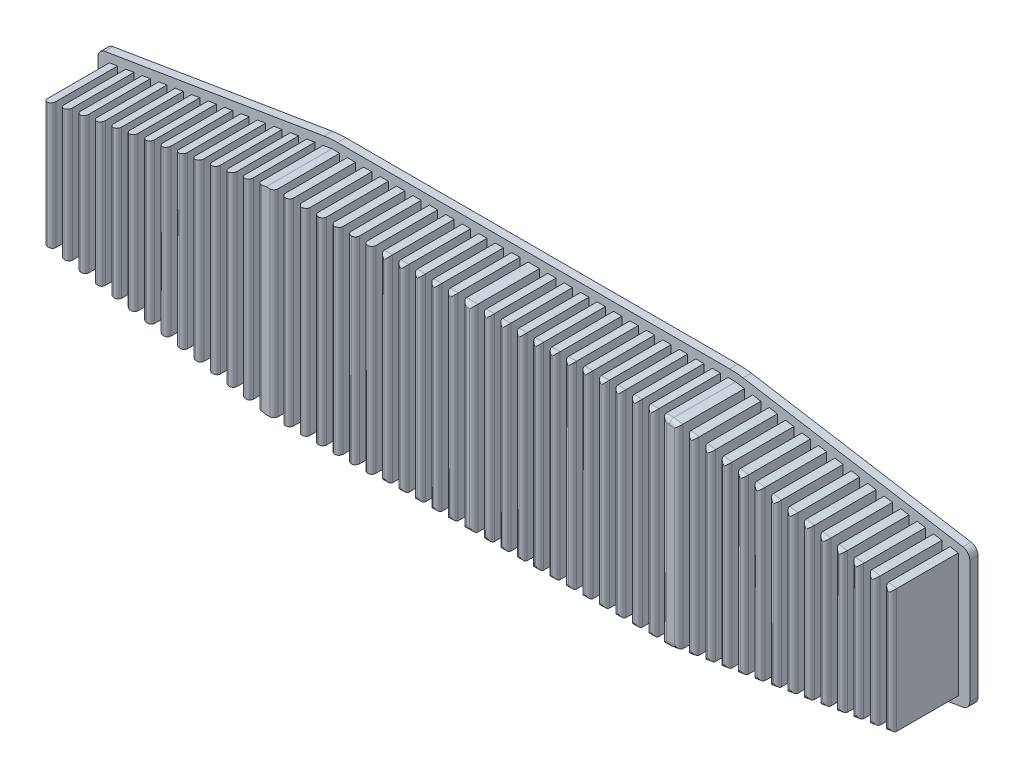
SolidWorks part; units mm, degrees
material "moto_Chrome Stainless Steel"
ref_plane "Front Plane" through (0, 0, 0) normal (0, 0, 1) x (1, 0, 0)
ref_plane "Top Plane" through (0, 0, 0) normal (0, 1, 0) x (1, 0, 0)
ref_plane "Right Plane" through (0, 0, 0) normal (1, 0, 0) x (0, 0, -1)
sketch "Sketch1" plane through (0, 0, 0) normal (0, 0, 1) x (1, 0, 0)
  line L12 (-24.854, 15) -> (-55, 10)
  line L14 (55, 10) -> (24.7913, 15)
  line L16 (-24.854, 15) -> (24.7913, 15)
  line L25 (0, 0) -> (4.6771, 0)
  line L26 (55, -10) -> (24.7913, -15)
  line L27 (-24.854, -15) -> (24.7913, -15)
  line L28 (-24.854, -15) -> (-55, -10)
  line L29 (-24.6892, 13) -> (-53, 8.3044)
  line L30 (-53, 8.3044) -> (-53, -8.3044)
  line L31 (-24.6892, -13) -> (-53, -8.3044)
  line L32 (-24.6892, -13) -> (24.6269, -13)
  line L33 (53, -8.3038) -> (24.6269, -13)
  line L34 (53, 8.3038) -> (53, -8.3038)
  line L35 (53, 8.3038) -> (24.6269, 13)
  line L36 (-55, 10) -> (-55, -10)
  line L37 (55, 10) -> (55, -10)
  line L38 (-24.6892, 13) -> (24.6269, 13)
  line L39 (-24.6069, 12) -> (-52, 7.4566)
  line L40 (-52, 7.4566) -> (-52, -7.4566)
  line L41 (-24.6069, -12) -> (-52, -7.4566)
  line L42 (-24.6069, -12) -> (24.5447, -12)
  line L43 (52, -7.4557) -> (24.5447, -12)
  line L44 (52, 7.4557) -> (52, -7.4557)
  line L45 (52, 7.4557) -> (24.5447, 12)
  line L46 (-24.6069, 12) -> (24.5447, 12)
  line L47 (-24.6069, 12) -> (-24.6069, -12)
  line L48 (6.6929, 12) -> (6.6929, -12)
  line L49 (-23.6069, 12) -> (-23.6069, -12)
  line L50 (-25.6069, 11.8341) -> (-25.6069, -11.8341)
  line L51 (0, 0) -> (0, 3.5519)
  line L52 (-7.6929, 12) -> (-7.6929, -12)
  line L53 (-8.6929, 12) -> (-8.6929, -12)
  line L54 (-9.6929, 12) -> (-9.6929, -12)
  line L55 (-10.6929, 12) -> (-10.6929, -12)
  line L56 (-11.6929, 12) -> (-11.6929, -12)
  line L57 (-12.6929, 12) -> (-12.6929, -12)
  line L58 (-13.6929, 12) -> (-13.6929, -12)
  line L59 (-14.6929, 12) -> (-14.6929, -12)
  line L60 (-15.6929, 12) -> (-15.6929, -12)
  line L61 (-16.6929, 12) -> (-16.6929, -12)
  line L62 (-17.6929, 12) -> (-17.6929, -12)
  line L63 (-18.6929, 12) -> (-18.6929, -12)
  line L64 (-19.6929, 12) -> (-19.6929, -12)
  line L65 (-20.6929, 12) -> (-20.6929, -12)
  line L66 (-21.6929, 12) -> (-21.6929, -12)
  line L67 (-22.6929, 12) -> (-22.6929, -12)
  line L68 (-26.6069, 11.6683) -> (-26.6069, -11.6683)
  line L69 (-27.6069, 11.5024) -> (-27.6069, -11.5024)
  line L70 (-28.6069, 11.3366) -> (-28.6069, -11.3366)
  line L71 (-29.6069, 11.1707) -> (-29.6069, -11.1707)
  line L72 (-30.6069, 11.0048) -> (-30.6069, -11.0048)
  line L73 (-31.6069, 10.839) -> (-31.6069, -10.839)
  line L74 (-32.6069, 10.6731) -> (-32.6069, -10.6731)
  line L75 (-33.6069, 10.5073) -> (-33.6069, -10.5073)
  line L76 (-34.6069, 10.3414) -> (-34.6069, -10.3414)
  line L77 (-35.6069, 10.1755) -> (-35.6069, -10.1755)
  line L78 (-36.6069, 10.0097) -> (-36.6069, -10.0097)
  line L79 (-37.6069, 9.8438) -> (-37.6069, -9.8438)
  line L80 (-38.6069, 9.678) -> (-38.6069, -9.678)
  line L81 (-39.6069, 9.5121) -> (-39.6069, -9.5121)
  line L82 (-40.6069, 9.3463) -> (-40.6069, -9.3463)
  line L83 (-41.6069, 9.1804) -> (-41.6069, -9.1804)
  line L84 (-42.6069, 9.0145) -> (-42.6069, -9.0145)
  line L85 (-43.6069, 8.8487) -> (-43.6069, -8.8487)
  line L86 (-44.6069, 8.6828) -> (-44.6069, -8.6828)
  line L87 (-45.6069, 8.517) -> (-45.6069, -8.517)
  line L88 (-46.6069, 8.3511) -> (-46.6069, -8.3511)
  line L89 (-47.6069, 8.1852) -> (-47.6069, -8.1852)
  line L90 (-48.6069, 8.0194) -> (-48.6069, -8.0194)
  line L91 (-49.6069, 7.8535) -> (-49.6069, -7.8535)
  line L92 (-50.6069, 7.6877) -> (-50.6069, -7.6877)
  line L93 (-51.6069, 7.5218) -> (-51.6069, -7.5218)
  line L94 (-6.6929, 12) -> (-6.6929, -12)
  line L95 (-5.6929, 12) -> (-5.6929, -12)
  line L96 (-4.6929, 12) -> (-4.6929, -12)
  line L97 (-3.6929, 12) -> (-3.6929, -12)
  line L98 (-2.6929, 12) -> (-2.6929, -12)
  line L99 (-1.6929, 12) -> (-1.6929, -12)
  line L100 (-0.6929, 12) -> (-0.6929, -12)
  line L101 (5.6929, 12) -> (5.6929, -12)
  line L102 (4.6929, 12) -> (4.6929, -12)
  line L103 (3.6929, 12) -> (3.6929, -12)
  line L104 (24.6069, 12) -> (-24.5447, 12)
  line L105 (-52, 7.4557) -> (-24.5447, 12)
  line L106 (-52, 7.4557) -> (-52, -7.4557)
  line L107 (-52, -7.4557) -> (-24.5447, -12)
  line L108 (24.6069, -12) -> (-24.5447, -12)
  line L109 (24.6069, -12) -> (52, -7.4566)
  line L110 (52, 7.4566) -> (52, -7.4566)
  line L111 (24.6069, 12) -> (52, 7.4566)
  line L112 (2.6929, 12) -> (2.6929, -12)
  line L113 (1.6929, 12) -> (1.6929, -12)
  line L114 (0.6929, 12) -> (0.6929, -12)
  line L115 (7.6929, 12) -> (7.6929, -12)
  line L116 (8.6929, 12) -> (8.6929, -12)
  line L117 (9.6929, 12) -> (9.6929, -12)
  line L118 (10.6929, 12) -> (10.6929, -12)
  line L119 (11.6929, 12) -> (11.6929, -12)
  line L120 (12.6929, 12) -> (12.6929, -12)
  line L121 (13.6929, 12) -> (13.6929, -12)
  line L122 (14.6929, 12) -> (14.6929, -12)
  line L123 (15.6929, 12) -> (15.6929, -12)
  line L124 (16.6929, 12) -> (16.6929, -12)
  line L125 (17.6929, 12) -> (17.6929, -12)
  line L126 (18.6929, 12) -> (18.6929, -12)
  line L127 (19.6929, 12) -> (19.6929, -12)
  line L128 (20.6929, 12) -> (20.6929, -12)
  line L129 (21.6929, 12) -> (21.6929, -12)
  line L130 (22.6929, 12) -> (22.6929, -12)
  line L131 (23.6069, 12) -> (23.6069, -12)
  line L132 (24.6069, 12) -> (24.6069, -12)
  line L133 (25.6069, 11.8341) -> (25.6069, -11.8341)
  line L134 (26.6069, 11.6683) -> (26.6069, -11.6683)
  line L135 (27.6069, 11.5024) -> (27.6069, -11.5024)
  line L136 (28.6069, 11.3366) -> (28.6069, -11.3366)
  line L137 (29.6069, 11.1707) -> (29.6069, -11.1707)
  line L138 (30.6069, 11.0048) -> (30.6069, -11.0048)
  line L139 (31.6069, 10.839) -> (31.6069, -10.839)
  line L140 (32.6069, 10.6731) -> (32.6069, -10.6731)
  line L141 (33.6069, 10.5073) -> (33.6069, -10.5073)
  line L142 (34.6069, 10.3414) -> (34.6069, -10.3414)
  line L143 (35.6069, 10.1755) -> (35.6069, -10.1755)
  line L144 (36.6069, 10.0097) -> (36.6069, -10.0097)
  line L145 (37.6069, 9.8438) -> (37.6069, -9.8438)
  line L146 (38.6069, 9.678) -> (38.6069, -9.678)
  line L147 (39.6069, 9.5121) -> (39.6069, -9.5121)
  line L148 (40.6069, 9.3463) -> (40.6069, -9.3463)
  line L149 (41.6069, 9.1804) -> (41.6069, -9.1804)
  line L150 (42.6069, 9.0145) -> (42.6069, -9.0145)
  line L151 (43.6069, 8.8487) -> (43.6069, -8.8487)
  line L152 (44.6069, 8.6828) -> (44.6069, -8.6828)
  line L153 (45.6069, 8.517) -> (45.6069, -8.517)
  line L154 (46.6069, 8.3511) -> (46.6069, -8.3511)
  line L155 (47.6069, 8.1852) -> (47.6069, -8.1852)
  line L156 (48.6069, 8.0194) -> (48.6069, -8.0194)
  line L157 (49.6069, 7.8535) -> (49.6069, -7.8535)
  line L158 (50.6069, 7.6877) -> (50.6069, -7.6877)
  line L159 (51.6069, 7.5218) -> (51.6069, -7.5218)
  point P3 (-55, 0)
  point P7 (55, 0)
  dimension "D1" = 10
  dimension "D2" = 10
  dimension "D3" = 15
  dimension "D4" = 2
  dimension "D5" = 1
  dimension "D6" = 1
  dimension "D7" = 1
  dimension "D8" = 1
  dimension "D9" = 1
  dimension "D10" = 1
  dimension "D11" = 1
  dimension "D12" = 1
  dimension "D13" = 1
  dimension "D14" = 1
  dimension "D15" = 1
  dimension "D16" = 1
  dimension "D17" = 1
  dimension "D18" = 1
  dimension "D19" = 1
  dimension "D20" = 1
  dimension "D21" = 1
  dimension "D22" = 1
  dimension "D23" = 1
  dimension "D24" = 1
  dimension "D25" = 1
  dimension "D26" = 1
  dimension "D27" = 1
  dimension "1" = 1
  dimension "D28" = 1
  dimension "D29" = 1
  dimension "D30" = 1
  dimension "D31" = 1
  dimension "D32" = 1
  dimension "D33" = 1
  dimension "D34" = 1
  dimension "D35" = 1
  dimension "D36" = 1
  dimension "D37" = 1
  dimension "D38" = 1
  dimension "D39" = 1
  dimension "D40" = 1
  dimension "D41" = 1
  dimension "D42" = 1
  dimension "D43" = 1
  dimension "D44" = 1
  dimension "D45" = 1
  dimension "D46" = 1
  dimension "D47" = 1
  dimension "D48" = 1
  dimension "D49" = 1
  dimension "D50" = 1
  dimension "D51" = 1
  dimension "D52" = 1
  dimension "D54" = 1
  dimension "D55" = 1
extrude "Boss-Extrude1" add sketch "Sketch1" against normal blind 3 contours L37 L14 L16 L12 L36 L28 L27 L26 L29 L38 L35 L34 L33 L32 L31 L30 region at (-0.0314, 13.8598, 0)
sketch "Sketch3" plane through (0, 0, 0) normal (0, 0, 1) x (1, 0, 0)
  line L44 (-53, 8.3044) -> (-53, -8.3044)
  line L45 (-53, -8.3044) -> (-24.6892, -13)
  line L46 (-24.6892, -13) -> (24.6269, -13)
  line L47 (24.6269, -13) -> (53, -8.3038)
  line L48 (53, -8.3038) -> (53, 8.3038)
  line L49 (53, 8.3038) -> (24.6269, 13)
  line L50 (24.6269, 13) -> (-24.6892, 13)
  line L51 (-24.6892, 13) -> (-53, 8.3044)
  line L52 (-53, 8.3044) -> (-53, -8.3044)
  line L53 (-53, -8.3044) -> (-24.6892, -13)
  line L54 (-24.6892, -13) -> (24.6269, -13)
  line L55 (24.6269, -13) -> (53, -8.3038)
  line L56 (53, -8.3038) -> (53, 8.3038)
  line L57 (53, 8.3038) -> (24.6269, 13)
  line L58 (24.6269, 13) -> (-24.6892, 13)
  line L59 (-24.6892, 13) -> (-53, 8.3044)
  dimension "D1" = 0
extrude "Boss-Extrude2" add sketch "Sketch3" against normal blind 1
extrude "Cut-Extrude1" cut sketch "Sketch1<5>" against normal blind 3 contours L37 L14 L16 L12 L36 L28 L27 L26 L29 L38 L35 L34 L33 L32 L31 L30 region at (-0.0314, 13.8598, 0)
sketch "Sketch1<5>" plane through (0, 0, 0) normal (0, 0, 1) x (1, 0, 0) same geometry as "Sketch1"
extrude "Boss-Extrude4" add sketch "Sketch1<7>" along normal blind 8 contours L93 L107 L92 L105 | L91 L107 L90 L105 | L89 L107 L88 L105 | L87 L107 L86 L105 | L85 L107 L84 L105 | L83 L107 L82 L105 | L81 L107 L80 L105 | L79 L107 L78 L105 | L77 L107 L76 L105 | L75 L107 L74 L105 | L73 L107 L72 L105 | L71 L107 L70 L105 | L69 L107 L68 L105 | L50 L107 L47 L105 | L47 L107 L42 L49 L46 L105 | L46 L67 L42 L66 | L46 L65 L42 L64 | L46 L63 L42 L62 | L46 L61 L42 L60 | L46 L59 L42 L58 | L46 L57 L42 L56 | L46 L55 L42 L54 | L46 L53 L42 L52 | L95 L46 L94 L42 | L97 L46 L96 L42 | L99 L46 L98 L42 | L114 L46 L100 L42 | L104 L113 L25 L112 | L25 L113 L108 L112 | L46 L103 L42 L102 | L46 L101 L42 L48 | L116 L104 L115 L108 | L133 L45 L132 L43 | L132 L45 L104 L131 L108 L43 | L130 L104 L129 L108 | L128 L104 L127 L108 | L126 L104 L125 L108 | L124 L104 L123 L108 | L122 L104 L121 L108 | L120 L104 L119 L108 | L118 L104 L117 L108 | L135 L45 L134 L43 | L137 L45 L136 L43 | L139 L45 L138 L43 | L141 L45 L140 L43 | L143 L45 L142 L43 | L145 L45 L144 L43 | L147 L45 L146 L43 | L149 L45 L148 L43 | L151 L45 L150 L43 | L153 L45 L152 L43 | L155 L45 L154 L43 | L157 L45 L156 L43 | L159 L45 L158 L43 region at (0.4525, -6, 0) region at (2.1929, 6, 0) region at (2.1929, -6, 0) region at (3.9331, 6, 0) region at (-2.1929, 0, 0) region at (-4.1929, 0, 0) region at (6.1929, 0, 0) region at (-6.1929, 0, 0) region at (8.1929, 0, 0) region at (-8.1929, 0, 0) region at (10.1929, 0, 0) region at (-10.1929, 0, 0) region at (12.1929, 0, 0) region at (-12.1929, 0, 0) region at (14.1929, 0, 0) region at (-14.1929, 0, 0) region at (16.1929, 0, 0) region at (-16.1929, 0, 0) region at (18.1929, 0, 0) region at (-18.1929, 0, 0) region at (20.1929, 0, 0) region at (-20.1929, 0, 0) region at (22.1929, 0, 0) region at (-22.1929, 0, 0) region at (24.1069, 0, 0) region at (-24.1069, 0, 0) region at (25.1057, 0, 0) region at (-25.1057, 0, 0) region at (27.1057, 0, 0) region at (-27.1057, 0, 0) region at (29.1056, 0, 0) region at (-29.1056, 0, 0) region at (31.1056, 0, 0) region at (-31.1056, 0, 0) region at (33.1056, 0, 0) region at (-33.1056, 0, 0) region at (35.1055, 0, 0) region at (-35.1055, 0, 0) region at (37.1055, 0, 0) region at (-37.1055, 0, 0) region at (39.1054, 0, 0) region at (-39.1054, 0, 0) region at (41.1054, 0, 0) region at (-41.1054, 0, 0) region at (43.1053, 0, 0) region at (-43.1053, 0, 0) region at (45.1053, 0, 0) region at (-45.1053, 0, 0) region at (47.1052, 0, 0) region at (-47.1052, 0, 0) region at (49.1051, 0, 0) region at (-49.1051, 0, 0) region at (51.1051, 0, 0) region at (-51.1051, 0, 0)
sketch "Sketch1<7>" plane through (0, 0, 0) normal (0, 0, 1) x (1, 0, 0) same geometry as "Sketch1"
fillet "Fillet1" radius 1 4 edges at (53, -8.3038, -0.5) (53, 8.3038, -0.5) (-53, -8.3044, -0.5) (-53, 8.3044, -0.5)
fillet "Fillet2" radius 10 4 edges at (24.6269, 13, -0.5) (-24.6892, 13, -0.5) (-24.6892, -13, -0.5) (24.6269, -13, -0.5)
fillet "Fillet3" radius 0.5 166 edges at (31.1069, -10.9139, 8) (30.6069, 0, 8) (31.1069, 10.9139, 8) (31.6069, 0, 8) (33.1069, -10.5828, 8) (32.6069, 0, 8) (33.1069, 10.5828, 8) (33.6069, 0, 8) (35.1069, -10.2518, 8) (34.6069, 0, 8) (35.1069, 10.2518, 8) (35.6069, 0, 8) (37.1069, -9.9208, 8) (36.6069, 0, 8) (37.1069, 9.9208, 8) (37.6069, 0, 8) (39.1069, -9.5897, 8) (38.6069, 0, 8) (39.1069, 9.5897, 8) (39.6069, 0, 8) (41.1069, -9.2587, 8) (40.6069, 0, 8) (41.1069, 9.2587, 8) (41.6069, 0, 8) (43.1069, -8.9277, 8) (42.6069, 0, 8) (43.1069, 8.9277, 8) (43.6069, 0, 8) (45.1069, -8.5966, 8) (44.6069, 0, 8) (45.1069, 8.5966, 8) (45.6069, 0, 8) (47.1069, -8.2656, 8) (46.6069, 0, 8) (47.1069, 8.2656, 8) (47.6069, 0, 8) (49.1069, -7.9346, 8) (48.6069, 0, 8) (49.1069, 7.9346, 8) (49.6069, 0, 8) (51.1069, -7.6036, 8) (50.6069, 0, 8) (51.1069, 7.6036, 8) (51.6069, 0, 8) (29.1069, -11.2449, 8) (28.6069, 0, 8) (29.1069, 11.2449, 8) (29.6069, 0, 8) (27.1069, -11.5759, 8) (26.6069, 0, 8) (27.1069, 11.5759, 8) (27.6069, 0, 8) (10.1929, -12, 8) (9.6929, 0, 8) (10.1929, 12, 8) (10.6929, 0, 8) (12.1929, -12, 8) (11.6929, 0, 8) (12.1929, 12, 8) (12.6929, 0, 8) (14.1929, -12, 8) (13.6929, 0, 8) (14.1929, 12, 8) (14.6929, 0, 8) (16.1929, -12, 8) (15.6929, 0, 8) (16.1929, 12, 8) (16.6929, 0, 8) (18.1929, -12, 8) (17.6929, 0, 8) (18.1929, 12, 8) (18.6929, 0, 8) (20.1929, -12, 8) (19.6929, 0, 8) (20.1929, 12, 8) (20.6929, 0, 8) (22.1929, -12, 8) (21.6929, 0, 8) (22.1929, 12, 8) (22.6929, 0, 8) (25.0758, -11.9121, 8) (24.0758, -12, 8) (23.6069, 0, 8) (24.0758, 12, 8) (25.0758, 11.9121, 8) (25.6069, 0, 8) (8.1929, -12, 8) (7.6929, 0, 8) (8.1929, 12, 8) (8.6929, 0, 8) (6.6929, 0, 8) (6.1929, -12, 8) (5.6929, 0, 8) (6.1929, 12, 8) (4.6929, 0, 8) (4.1929, -12, 8) (3.6929, 0, 8) (4.1929, 12, 8) (2.6929, 0, 8) (2.1929, -12, 8) (1.6929, 0, 8) (2.1929, 12, 8) (-0.6929, 0, 8) (0, 12, 8) (0.6929, 0, 8) (0, -12, 8) (-2.1929, -12, 8) (-2.6929, 0, 8) (-2.1929, 12, 8) (-1.6929, 0, 8) (-4.1929, -12, 8) (-4.6929, 0, 8) (-4.1929, 12, 8) (-3.6929, 0, 8) (-6.1929, -12, 8) (-6.6929, 0, 8) (-6.1929, 12, 8) (-5.6929, 0, 8) (-7.6929, 0, 8) (-8.1929, -12, 8) (-8.6929, 0, 8) (-8.1929, 12, 8) (-9.6929, 0, 8) (-10.1929, -12, 8) (-10.6929, 0, 8) (-10.1929, 12, 8) (-11.6929, 0, 8) (-12.6929, 0, 8) (-13.6929, 0, 8) (-14.6929, 0, 8) (-15.6929, 0, 8) (-16.6929, 0, 8) (-17.6929, 0, 8) (-18.6929, 0, 8) (-19.6929, 0, 8) (-20.6929, 0, 8) (-21.6929, 0, 8) (-22.6929, 0, 8) (-23.6069, 0, 8) (-25.6069, 0, 8) (-26.6069, 0, 8) (-27.6069, 0, 8) (-28.6069, 0, 8) (-29.6069, 0, 8) (-30.6069, 0, 8) (-31.6069, 0, 8) (-32.6069, 0, 8) (-33.6069, 0, 8) (-34.6069, 0, 8) (-35.6069, 0, 8) (-36.6069, 0, 8) (-37.6069, 0, 8) (-38.6069, 0, 8) (-39.6069, 0, 8) (-40.6069, 0, 8) (-41.6069, 0, 8) (-42.6069, 0, 8) (-43.6069, 0, 8) (-44.6069, 0, 8) (-45.6069, 0, 8) (-46.6069, 0, 8) (-47.6069, 0, 8) (-49.6069, 0, 8) (-48.6069, 0, 8) (-50.6069, 0, 8) (-51.6069, 0, 8)
